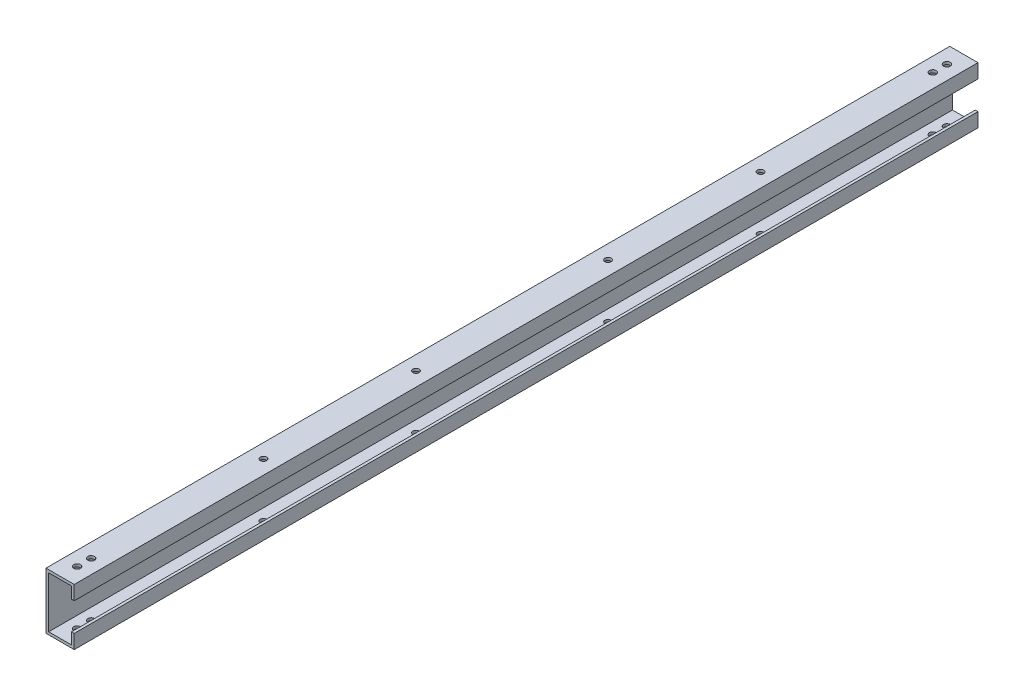
SolidWorks part; units mm, degrees
material "AISI 1020 Acero laminado en frío"
ref_plane "Alzado" through (0, 0, 0) normal (0, 0, 1) x (1, 0, 0)
ref_plane "Planta" through (0, 0, 0) normal (0, 1, 0) x (1, 0, 0)
ref_plane "Vista lateral" through (0, 0, 0) normal (1, 0, 0) x (0, 0, -1)
sketch "Croquis1" plane through (0, 0, 0) normal (0, 0, 1) x (1, 0, 0)
  line L0 (-20.2375, -45.2375) -> (-20.2375, 45.2375)
  line L1 (-25, -50) -> (25, -50)
  line L2 (-25, -50) -> (-25, 50)
  line L3 (-25, 50) -> (25, 50)
  line L4 (25, -50) -> (25, 50)
  line L5 (-25, -50) -> (25, 50) construction
  line L6 (-25, 50) -> (25, -50) construction
  line L7 (-20.2375, 45.2375) -> (20.2375, 45.2375)
  line L8 (20.2375, -45.2375) -> (20.2375, 45.2375)
  line L9 (-20.2375, -45.2375) -> (20.2375, -45.2375)
  point P0 (0, 0)
  dimension "D1" = 100
  dimension "D2" = 50
  dimension "D3" = 4.7625
extrude "Saliente-Extruir1" add sketch "Croquis1" along normal mid plane 1600
sketch "Croquis2" plane through (25, 0, 0) normal (1, 0, 0) x (0, 0, -1)
  line L1 (800, 25) -> (-800, 25)
  line L2 (800, 25) -> (800, -25)
  line L3 (800, -25) -> (-800, -25)
  line L4 (-800, 25) -> (-800, -25)
  line L5 (800, 25) -> (-800, -25) construction
  line L6 (800, -25) -> (-800, 25) construction
  point P0 (0, 0)
  dimension "D1" = 1600
  dimension "D2" = 50
extrude "Cortar-Extruir1" cut sketch "Croquis2" against normal blind 5
hole_wizard "Taladro de margen para 7/161" positions "Croquis9" profile "Croquis10" hole size "7/16" standard "Ansi Inch"
sketch "Croquis9" plane through (349.3117, -55.2375, 12.2412) normal (0, -1, 0) x (-1, 0, 0)
  point P0 (-600.6883, 757.2412)
  point P3 (-600.6883, 782.2412)
  point P6 (349.3117, 782.2412)
  point P9 (349.3117, 757.2412)
sketch "Croquis10" plane through (950, -55.2375, -745) normal (1, 0, 0) x (0, 0, -1)
  line L0 (0, 0) -> (0, 155.0766)
  line L1 (0, 155.0766) -> (5.9525, 151.5)
  line L2 (5.9525, 151.5) -> (5.9525, 0)
  line L3 (5.9525, 0) -> (0, 0)
  line L4 (0, 155.0766) -> (-5.9525, 151.5) construction
  line L5 (0, -6.35) -> (0, 107.95) construction
  dimension "Diámetro de taladro" = 11.905
  dimension "Profundidad de taladro" = 151.5
  dimension "Ángulo de perforador" = 118
hole_wizard "Taladro de margen para 7/162" positions "Croquis11" profile "Croquis12" hole size "7/16" standard "Ansi Inch"
sketch "Croquis11" plane through (600.6883, -55.2375, -12.2412) normal (0, -1, 0) x (1, 0, 0)
  point P0 (-600.6883, 757.2412)
  point P3 (-600.6883, 782.2412)
  point P6 (349.3117, 782.2412)
  point P9 (349.3117, 757.2412)
sketch "Croquis12" plane through (0, -55.2375, 745) normal (1, 0, 0) x (0, 0, -1)
  line L0 (0, 0) -> (0, 155.0766)
  line L1 (0, 155.0766) -> (5.9525, 151.5)
  line L2 (5.9525, 151.5) -> (5.9525, 0)
  line L3 (5.9525, 0) -> (0, 0)
  line L4 (0, 155.0766) -> (-5.9525, 151.5) construction
  line L5 (0, -6.35) -> (0, 107.95) construction
  dimension "Diámetro de taladro" = 11.905
  dimension "Profundidad de taladro" = 151.5
  dimension "Ángulo de perforador" = 118
sketch "Croquis13" plane through (0, -50, 0) normal (0, -1, 0) x (1, 0, 0)
  line L0 (0, 868.3928) -> (0, -492.4134) construction
  line L1 (-32.596, -440) -> (35.2772, -440) construction
  line L2 (-36.6904, -170) -> (33.2586, -170) construction
  line L3 (-25, -800) -> (25, -800) construction
  line L4 (121.0257, 0) -> (-136.3015, 0) construction
  circle A0 centre (0, -440) radius 5.5563
  circle A1 centre (0, -170) radius 5.5562
  circle A4 centre (0, 440) radius 5.5563
  circle A5 centre (0, 170) radius 5.5562
  dimension "D1" = 11.1125
  dimension "D2" = 360
  dimension "D3" = 630
extrude "Cortar-Extruir2" cut sketch "Croquis13" against normal blind 120
